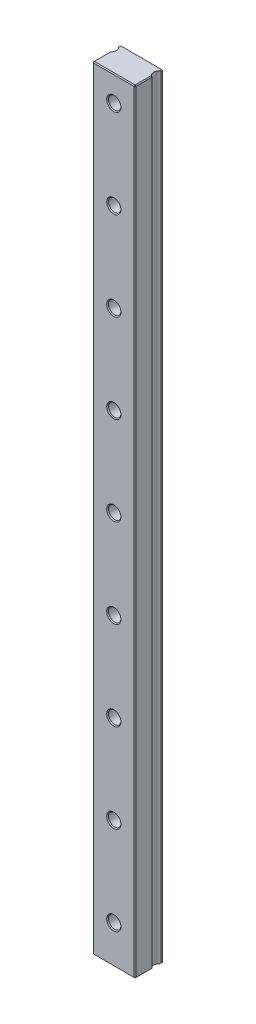
SolidWorks part; units mm, degrees
material "Chrome Stainless Steel"
ref_plane "Front" through (0, 0, 0) normal (0, 0, 1) x (1, 0, 0)
ref_plane "Top" through (0, 0, 0) normal (0, 1, 0) x (1, 0, 0)
ref_plane "Right" through (0, 0, 0) normal (1, 0, 0) x (0, 0, -1)
sketch "Sketch1" plane through (0, 0, 0) normal (0, 1, 0) x (1, 0, 0)
  line L0 (-6, 4) -> (-6, 2.75)
  line L1 (-6, 4) -> (6, 4)
  line L2 (-6, 4) -> (-6, -4)
  line L3 (-6, -4) -> (6, -4)
  line L4 (6, 4) -> (6, -4)
  line L5 (-6, 4) -> (6, -4) construction
  line L6 (-6, -4) -> (6, 4) construction
  line L7 (6, 4) -> (6, 2)
  line L8 (-6.75, 2) -> (6.75, 2) construction
  circle A0 centre (-6, 2) radius 0.75 construction
  circle A1 centre (6, 2) radius 0.75 construction
  arc A2 (-6, 0.701) -> (-6, 3.299) centre (-6.75, 2) ccw
  arc A3 (6, 3.299) -> (6, 0.701) centre (6.75, 2) ccw
  point P0 (0, 0)
  dimension "D1" = 8
  dimension "D2" = 12
extrude "Boss-Extrude1" add sketch "Sketch1" along normal blind 218 contours A3 L4 L1 L0 A2 L2 L3 region at (0, 0, 0.0593)
sketch "Sketch3" plane through (0, 0, -4) normal (0, 0, -1) x (-1, 0, 0)
  line L0 (6, 218) -> (6, 0) construction
  line L1 (-6, 0) -> (6, 0) construction
  line L2 (-6, 0) -> (-6, 10.75) construction
  line L3 (-6, 10.75) -> (6, 10.75) construction
  line L4 (6, 0) -> (6, 10.75) construction
  line L5 (-6, 0) -> (6, 10.75) construction
  line L6 (-6, 10.75) -> (6, 0) construction
  circle A0 centre (0, 10.75) radius 3.25
  circle A1 centre (0, 10.75) radius 1.75
  circle A2 centre (0, 35.75) radius 3.25
  circle A3 centre (0, 35.75) radius 1.75
  circle A4 centre (0, 60.75) radius 3.25
  circle A5 centre (0, 60.75) radius 1.75
  circle A6 centre (0, 85.75) radius 3.25
  circle A7 centre (0, 85.75) radius 1.75
  circle A8 centre (0, 110.75) radius 3.25
  circle A9 centre (0, 110.75) radius 1.75
  circle A10 centre (0, 135.75) radius 3.25
  circle A11 centre (0, 135.75) radius 1.75
  circle A12 centre (0, 160.75) radius 3.25
  circle A13 centre (0, 160.75) radius 1.75
  circle A14 centre (0, 185.75) radius 3.25
  circle A15 centre (0, 185.75) radius 1.75
  circle A16 centre (0, 210.75) radius 3.25
  circle A17 centre (0, 210.75) radius 1.75
  circle A18 centre (0, 235.75) radius 3.25
  circle A19 centre (0, 235.75) radius 1.75
  circle A20 centre (0, 260.75) radius 3.25
  circle A21 centre (0, 260.75) radius 1.75
  circle A22 centre (0, 285.75) radius 3.25
  circle A23 centre (0, 285.75) radius 1.75
  circle A24 centre (0, 310.75) radius 3.25
  circle A25 centre (0, 310.75) radius 1.75
  circle A26 centre (0, 335.75) radius 3.25
  circle A27 centre (0, 335.75) radius 1.75
  point P4 (0, 5.375)
  dimension "D1" = 14
extrude "Cut-Extrude3" cut sketch "Sketch3" against normal blind 8.5 contours A27 | A25 | A23 | A21 | A19 | A17 | A15 | A13 | A9 | A7 | A5 | A3 | A11 | A1 region at (0, 35.75, -4) region at (0, 60.75, -4) region at (0, 85.75, -4) region at (0, 110.75, -4) region at (0, 160.75, -4) region at (0, 185.75, -4) region at (0, 210.75, -4) region at (0, 235.75, -4) region at (0, 260.75, -4) region at (0, 285.75, -4) region at (0, 310.75, -4) region at (0, 335.75, -4)
extrude "Cut-Extrude4" cut sketch "Sketch3<6>" against normal blind 4.5
sketch "Sketch3<6>" plane through (0, 0, -4) normal (0, 0, -1) x (-1, 0, 0) same geometry as "Sketch3"
chamfer "Chamfer3" distance 0.25 angle 45 43 edges at (-1.75, 210.75, 4) (-1.75, 185.75, 4) (-1.75, 160.75, 4) (-1.75, 135.75, 4) (-1.75, 110.75, 4) (-1.75, 85.75, 4) (-1.75, 60.75, 4) (-1.75, 35.75, 4) (-1.75, 10.75, 4) (0, 0, 4) (6, 0, 1.6495) (-6, 0, 1.6495) (6, 218, 1.6495) (-6, 218, 1.6495) (6, 109, 4) (0, 218, 4) (-6, 109, 4) (6, 0, -3.6495) (-6, 0, -3.6495) (0, 0, -4) (6, 218, -3.6495) (-6, 218, -3.6495) (-6, 109, -4) (0, 218, -4) (6, 109, -4) (-3.25, 210.75, -4) (-1.75, 210.75, 0.5) (-3.25, 185.75, -4) (-1.75, 185.75, 0.5) (-3.25, 160.75, -4) (-1.75, 160.75, 0.5) (-3.25, 135.75, -4) (-1.75, 135.75, 0.5) (-3.25, 110.75, -4) (-1.75, 110.75, 0.5) (-3.25, 85.75, -4) (-1.75, 85.75, 0.5) (-3.25, 60.75, -4) (-1.75, 60.75, 0.5) (-3.25, 35.75, -4) (-1.75, 35.75, 0.5) (-3.25, 10.75, -4) (-1.75, 10.75, 0.5)
